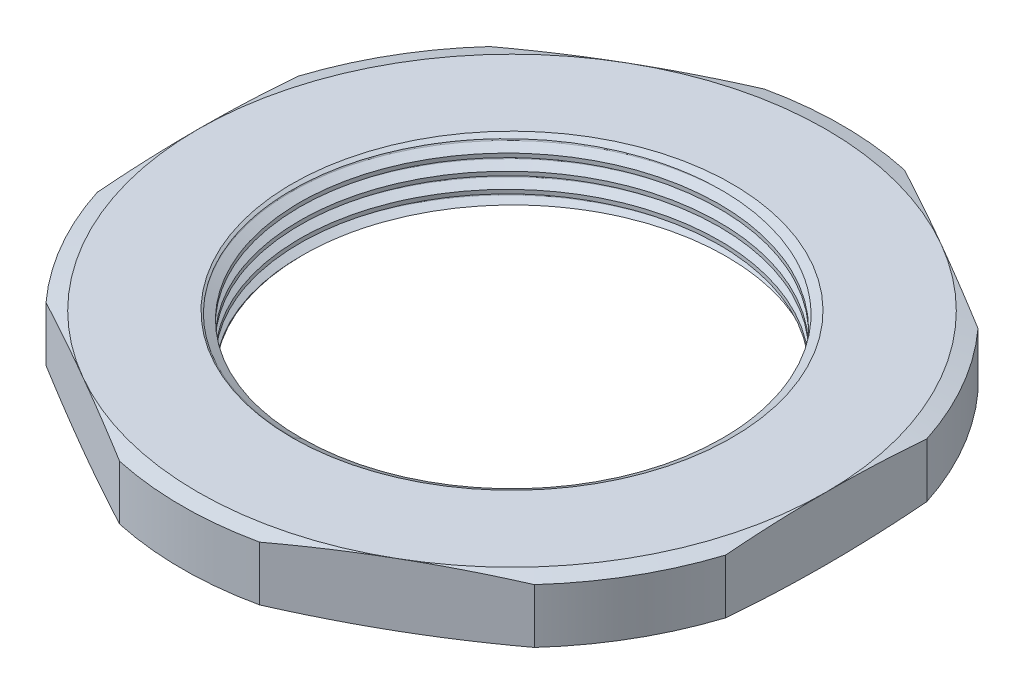
SolidWorks part; units mm, degrees
material "S355JR"
ref_plane "Front" through (0, 0, 0) normal (0, 0, 1) x (1, 0, 0)
ref_plane "Top" through (0, 0, 0) normal (0, 1, 0) x (1, 0, 0)
ref_plane "Right" through (0, 0, 0) normal (1, 0, 0) x (0, 0, -1)
sketch "Sketch1" plane through (0, 0, 0) normal (1, 0, 0) x (0, 0, -1)
  line L0 (-14, 2) -> (-20, 2)
  line L1 (-20, 2) -> (-20, -2)
  line L2 (-20, -2) -> (-14, -2)
  line L3 (-14, -2) -> (-13.3505, -1.625)
  line L4 (-13.3505, -1.625) -> (-13.3505, 1.625)
  line L5 (-13.3505, 1.625) -> (-14, 2)
  line L6 (-13.134, 2.5) -> (-13.3505, 2.5) construction
  line L7 (-13.134, 2.5) -> (-14, 2) construction
  line L8 (-14, 2) -> (-13.134, 1.5) construction
  line L9 (-13.134, 1.5) -> (-13.134, 2.5) construction
  line L10 (-13.3505, 2.5) -> (-13.567, 2.5) construction
  line L11 (-13.567, 2.5) -> (-13.7835, 2.5) construction
  line L12 (-13.7835, 2.5) -> (-14, 2.5) construction
  line L13 (-14, 2.5) -> (-14, 2) construction
  line L14 (0, 0) -> (0, -16192.1788) construction
  point P14 (-20, 0)
  dimension "D1" = 40
  dimension "D2" = 4
  dimension "D3" = 28
  dimension "D4" = 1
revolve "Revolve1" add sketch "Sketch1" angle 360 about L14
sketch "Sketch2" plane through (0, 2, 0) normal (0, 1, 0) x (1, 0, 0)
  line L1 (-20, -11.547) -> (0, -23.094)
  line L2 (0, -23.094) -> (20, -11.547)
  line L3 (20, -11.547) -> (20, 11.547)
  line L4 (20, 11.547) -> (0, 23.094)
  line L5 (0, 23.094) -> (-20, 11.547)
  line L6 (-20, 11.547) -> (-20, -11.547)
  circle A0 centre (0, 0) radius 20 construction
  circle A1 centre (0, 0) radius 20 construction
  circle A2 centre (0, 0) radius 14 construction
  circle A3 centre (0, 0) radius 14
extrude "Boss-Extrude1" add sketch "Sketch2" against normal up to surface (4 mm away) up to face at (0, -2, 14)
sketch "Sketch3" plane through (0, 0, 0) normal (1, 0, 0) x (0, 0, -1)
  line L0 (-23.094, 2) -> (-20, 2)
  line L1 (-20, 2) -> (-21, 1.7321)
  line L2 (-21, 1.7321) -> (-21, -1.7321)
  line L3 (-21, -1.7321) -> (-20, -2)
  line L4 (-20, -2) -> (-23.094, -2)
  line L5 (-23.094, -2) -> (-23.094, 2)
  line L6 (0, 0) -> (0, -4.8319) construction
  dimension "D1" = 15
  dimension "D2" = 42
revolve "Cut-Revolve1" cut sketch "Sketch3" angle 360 about L6
sketch "Sketch4" plane through (0, 2, 0) normal (0, 1, 0) x (1, 0, 0)
  circle A0 centre (0, 0) radius 13.3505 construction
  circle A1 centre (0, 0) radius 13.3505
curve "Helix/Spiral1" pitch 1 height 6 radius 13.3505 centre (0, 2, 0) axis (0, -1, 0) start towards (0, 0, 1)
sketch "Sketch5" plane through (0, 0, 0) normal (1, 0, 0) x (0, 0, -1)
  line L0 (-13.3505, 1.625) -> (-13.8917, 1.9375)
  line L2 (-13.3505, 1.625) -> (-14, 2) construction
  line L3 (-13.134, 2.5) -> (-14, 2) construction
  line L4 (-13.8917, 2.0625) -> (-13.3505, 2.375)
  line L5 (-13.3505, 2.375) -> (-13.134, 2.375)
  line L6 (-13.134, 1.5) -> (-13.134, 2.5) construction
  line L7 (-13.134, 2.375) -> (-13.134, 1.625)
  line L8 (-13.134, 1.625) -> (-13.3505, 1.625)
  line L9 (-13.8917, 2.5) -> (-13.8917, 2.0625) construction
  line L10 (-13.7835, 2.5) -> (-14, 2.5) construction
  arc A0 (-13.8917, 1.9375) -> (-13.8917, 2.0625) centre (-13.8557, 2) cw
sweep "Cut-Sweep1" cut profiles "Sketch5" path "Helix/Spiral1" align with end faces yes
